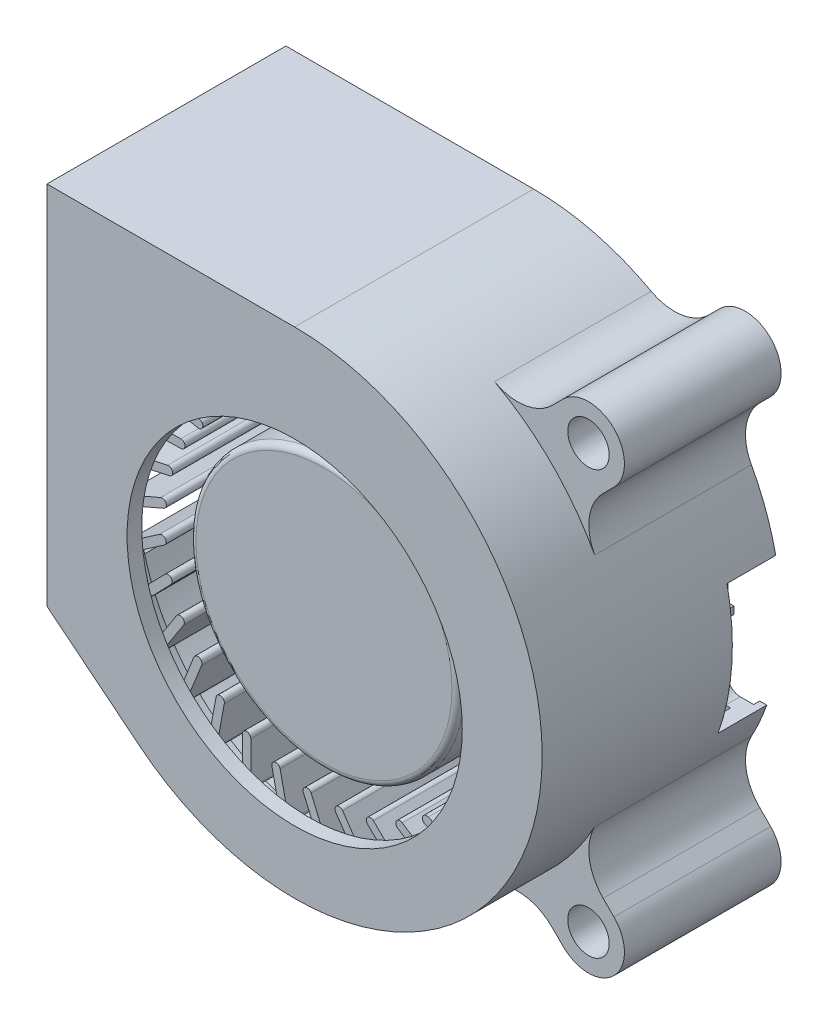
SolidWorks part; units mm, degrees
ref_plane "Спереди" through (0, 0, 0) normal (0, 0, 1) x (1, 0, 0)
ref_plane "Сверху" through (0, 0, 0) normal (0, 1, 0) x (1, 0, 0)
ref_plane "Справа" through (0, 0, 0) normal (1, 0, 0) x (0, 0, -1)
sketch "Эскиз1" plane through (0, 0, 0) normal (0, 0, 1) x (1, 0, 0)
  line L0 (-20.3193, 21.7023) -> (-20.3193, -8.2977)
  line L1 (-20.3193, -8.2977) -> (-12.7335, -14.4075)
  line L2 (-20.3193, 21.7023) -> (0, 21.7023)
  line L3 (0, 1.4023) -> (20.3, 21.7023) construction
  line L4 (20.3, 21.7023) -> (20.3, -18.8977) construction
  line L5 (20.3, -18.8977) -> (0, 1.4023) construction
  line L6 (20.3, -18.8977) -> (-20.3, -18.8977) construction
  line L7 (-20.3, -18.8977) -> (0, 1.4023) construction
  line L8 (-19.436, -13.8618) -> (-16.7482, -11.174)
  line L9 (-15.264, -18.0337) -> (-12.1159, -14.8856)
  line L10 (17.35, -18.8977) -> (0, -18.8977)
  line L11 (12.1159, -14.8856) -> (15.264, -18.0337)
  line L12 (19.436, -13.8618) -> (16.2879, -10.7137)
  line L13 (15.264, 20.8382) -> (12.1159, 17.6901)
  line L14 (19.436, 16.6663) -> (16.2879, 13.5182)
  line L15 (-20.3193, 20.5023) -> (0.1052, 20.502)
  line L16 (-17.6473, -5.904) -> (-20.3193, -7.0102)
  circle A0 centre (0, 0) radius 13.7477
  arc A1 (-12.7335, -14.4075) -> (0, 21.7023) centre (0, 1.4023) ccw
  circle A2 centre (17.35, 18.7523) radius 1.7
  circle A3 centre (-17.35, -15.9477) radius 1.7
  circle A4 centre (17.35, -15.9477) radius 1.7
  arc A5 (-19.436, -13.8618) -> (-15.264, -18.0337) centre (-17.35, -15.9477) ccw
  arc A6 (15.264, -18.0337) -> (19.436, -13.8618) centre (17.35, -15.9477) ccw
  arc A7 (19.436, 16.6663) -> (15.264, 20.8382) centre (17.35, 18.7523) ccw
  arc A8 (-17.6473, -5.904) -> (0.1052, 20.502) centre (0, 1.4023) ccw
  dimension "D1" = 30
  dimension "D2" = 20.3
  dimension "D3" = 27.4955
  dimension "D4" = 3.4
  dimension "D5" = 5.9
  dimension "D8" = 19.1
  dimension "D6" = 20.3193
  dimension "D7" = 1.4023
extrude "Бобышка-Вытянуть1" add sketch "Эскиз1" along normal blind 12.85 contours L14 A7 L13 A1 A2 | L11 A6 L12 A1 A4 | L8 A5 L9 A1 L1 A3 region at (13.7718, 19.1823, 0) region at (-14.8114, -12.8784, 0) region at (17.7801, -12.3696, 0)
extrude "Бобышка-Вытянуть2" add sketch "Эскиз1<4>" along normal blind 1.7 separate body contours L16 A8 L15 L0 A0 | A0 region at (-10.107, 19.9532, 0) region at (0, 0, 0)
sketch "Эскиз1<4>" plane through (0, 0, 0) normal (0, 0, 1) x (1, 0, 0) same geometry as "Эскиз1"
extrude "Бобышка-Вытянуть3" add sketch "Эскиз1<5>" along normal blind 19.6 contours A8 L16 L0 L1 A1 L2 L15 region at (-10.1596, 21.128, 0)
sketch "Эскиз1<5>" plane through (0, 0, 0) normal (0, 0, 1) x (1, 0, 0) same geometry as "Эскиз1"
extrude "Бобышка-Вытянуть4" add sketch "Эскиз1<6>" against normal blind 1.2 from vertex contours L16 A8 L15 L0 A0 region at (-10.107, 19.9532, 0) starting at point (-20.3193, 20.5023, 19.6)
sketch "Эскиз1<6>" plane through (0, 0, 0) normal (0, 0, 1) x (1, 0, 0) same geometry as "Эскиз1"
sketch "Эскиз2" plane through (0, 0, 0) normal (0, 0, -1) x (-1, 0, 0)
  line L8 (-10.3957, -0.3) -> (-19.6807, -0.3)
  line L9 (-0.3, 10.3957) -> (-0.2869, 21.1544)
  line L10 (10.3957, 0.3) -> (19.8766, 0.3)
  line L11 (0.3, -10.3957) -> (0.301, -18.3496)
  line L12 (19.887, -8.0245) -> (12.3908, -13.9826)
  line L13 (19.8505, 21.1544) -> (19.8766, 0.3)
  line L14 (19.8505, 21.1544) -> (0.3001, 21.1544)
  line L15 (-10.3957, 0.3) -> (-19.7234, 0.3)
  line L16 (0.3, 10.3957) -> (0.3001, 21.1544)
  line L17 (10.3957, -0.3) -> (19.8773, -0.3)
  line L18 (-0.3, -10.3957) -> (-0.301, -18.3496)
  line L19 (19.8773, -0.3) -> (19.887, -8.0245)
  arc A0 (0.301, -18.3496) -> (12.3908, -13.9826) centre (0, 1.4023) ccw
  arc A1 (10.3957, 0.3) -> (0.3, 10.3957) centre (0, 0) ccw
  arc A2 (0, 21.7023) -> (-12.1159, 17.6901) centre (0, 1.4023) ccw construction
  arc A5 (-0.2869, 21.1544) -> (-19.7234, 0.3) centre (0, 1.4023) ccw
  circle A6 centre (0, 0) radius 9.8
  arc A8 (-0.3, 10.3957) -> (-10.3957, 0.3) centre (0, 0) ccw
  arc A12 (-19.6807, -0.3) -> (-0.301, -18.3496) centre (0, 1.4023) ccw
  arc A13 (-10.3957, -0.3) -> (-0.3, -10.3957) centre (0, 0) ccw
  arc A14 (0.3, -10.3957) -> (10.3957, -0.3) centre (0, 0) ccw
extrude "Вырез-Вытянуть1" cut sketch "Эскиз2" against normal blind 0.5
sketch "Эскиз3" plane through (0, 0, 0) normal (0, 0, -1) x (-1, 0, 0)
  line L1 (-25.6875, -5.3927) -> (-16.4308, -5.3927)
  line L2 (-25.6875, -5.3927) -> (-25.6875, 5.6073)
  line L3 (-25.6875, 5.6073) -> (-16.4308, 5.6073)
  line L4 (-16.4308, -5.3927) -> (-16.4308, 5.6073)
  line L5 (-25.6875, -5.3927) -> (-16.4308, 5.6073) construction
  line L6 (-25.6875, 5.6073) -> (-16.4308, -5.3927) construction
extrude "Вырез-Вытянуть2" cut sketch "Эскиз3" against normal blind 4
sketch "Эскиз4" plane through (0, 0, 0) normal (0, 0, -1) x (-1, 0, 0)
  line L0 (1.85, -12.5557) -> (3.7573, -12.5557)
  line L2 (-3.7736, -9.046) -> (-3.7736, -12.5557)
  line L3 (-3.7736, -12.5557) -> (-1.85, -12.5557)
  line L4 (3.7573, -9.0528) -> (3.7573, -12.5557)
  line L5 (-0.0082, -9.8) -> (3.7573, -12.5557) construction
  line L6 (-3.7736, -12.5557) -> (-0.0082, -9.8) construction
  line L7 (-1.85, -18.9877) -> (1.85, -18.9877)
  line L8 (-1.85, -18.9877) -> (-1.85, -12.5557)
  line L10 (1.85, -18.9877) -> (1.85, -12.5557)
  line L11 (-1.85, -18.9877) -> (0, -14.4877) construction
  line L12 (0, -14.4877) -> (1.85, -18.9877) construction
  circle A0 centre (0, 0) radius 9.8 construction
  arc A1 (-3.7736, -9.046) -> (3.7573, -9.0528) centre (0, 0) ccw
  point P0 (-0.0082, -9.8)
  point P7 (0, -14.4877)
extrude "Вырез-Вытянуть3" cut sketch "Эскиз4" against normal blind 2
sketch "Эскиз5" plane through (0, -12.5557, 0) normal (0, 1, 0) x (1, 0, 0)
  line L0 (1.85, -1.7) -> (1.85, -2)
  line L1 (1.85, -2) -> (-1.85, -2)
  line L2 (-1.85, -2) -> (-1.85, -1.7)
  line L3 (2.8118, -1.7) -> (2.8118, -3.2)
  line L4 (1.85, -1.7) -> (3.7736, -1.7) construction
  line L5 (2.8118, -3.2) -> (-2.8036, -3.2)
  line L6 (-2.8036, -3.2) -> (-2.8036, -1.7)
  line L7 (-3.7573, -1.7) -> (-1.85, -1.7) construction
  line L8 (2.8118, -1.7) -> (1.85, -1.7)
  line L9 (-1.85, -1.7) -> (-2.8036, -1.7)
  dimension "D1" = 1.2
extrude "Бобышка-Вытянуть5" add sketch "Эскиз5" against normal up to next
fillet "Скругление1" radius 4 6 edges at (16.2879, 13.5182, 6.425) (12.1159, 17.6901, 6.425) (-12.1159, -14.8856, 6.425) (-16.7482, -11.174, 6.425) (16.2879, -10.7137, 6.425) (12.1159, -14.8856, 6.425)
fillet "Скругление2" radius 1 14 edges at (10.3957, -0.3, 0.25) (10.3957, 0.3, 0.25) (-19.887, -8.0245, 0.25) (-19.8773, -0.3, 0.25) (-10.3957, -0.3, 0.25) (-10.3957, 0.3, 0.25) (-19.8766, 0.3, 0.25) (-19.8505, 21.1544, 0.25) (-0.3001, 21.1544, 0.25) (0.2869, 21.1544, 0.25) (0.3, 10.3957, 0.25) (-0.3, 10.3957, 0.25) (16.4308, -5.3927, 1.1) (16.4308, 5.6073, 1.1)
ref_plane "Плоскость1" through (0, 0, 4.2) normal (0, 0, 1) x (1, 0, 0)
sketch "Эскиз6" plane through (0, 0, 4.2) normal (0, 0, 1) x (1, 0, 0)
  line L0 (-16.4475, 0) -> (-13.272, 1.3682) construction
  line L1 (-16.5836, 0.3159) -> (-13.4081, 1.6841)
  line L2 (-16.3114, -0.3159) -> (-13.1359, 1.0522)
  circle A0 centre (0, 0) radius 16.7732
  circle A1 centre (0, 0) radius 16.4475
  circle A2 centre (0, 0) radius 11
  arc A3 (-16.5836, 0.3159) -> (-16.3114, -0.3159) centre (-16.4475, 0) ccw
  arc A4 (-13.1359, 1.0522) -> (-13.4081, 1.6841) centre (-13.272, 1.3682) ccw
  point P7 (-14.8598, 0.6841)
extrude "Бобышка-Вытянуть6" add sketch "Эскиз6" along normal blind 1.2 separate body contours A4 L2 A3 A1 L1 A2 | L2 A4 L1 A1 A3 region at (0.1829, 15.9813, 4.2) region at (-14.7325, 0.7341, 4.2)
extrude "Бобышка-Вытянуть7" add sketch "Эскиз6<3>" along normal blind 13 contours L2 A4 L1 A1 A3 region at (-14.7325, 0.7341, 4.2)
sketch "Эскиз6<3>" plane through (0, 0, 4.2) normal (0, 0, 1) x (1, 0, 0) same geometry as "Эскиз6"
pattern_circular "Круговой массив6" count 32 over 360 about axis through (0, 0, 5.4) along (0, 0, -1) of "Бобышка-Вытянуть7"
extrude "Бобышка-Вытянуть8" add sketch "Эскиз6<4>" against normal blind 1.2 from offset 13 contours A3 L1 A1 A0 | L1 A3 A0 A1 region at (-16.7346, 0.2661, 4.2) region at (-16.5891, 0.0029, 4.2)
sketch "Эскиз6<4>" plane through (0, 0, 4.2) normal (0, 0, 1) x (1, 0, 0) same geometry as "Эскиз6"
extrude "Бобышка-Вытянуть9" add sketch "Эскиз6<5>" along normal blind 13 contours A2 region at (0, 0, 4.2)
sketch "Эскиз6<5>" plane through (0, 0, 4.2) normal (0, 0, 1) x (1, 0, 0) same geometry as "Эскиз6"
fillet "Скругление3" radius 0.5 1 edges at (11, 0, 17.2)
ref_axis "Eje1" through (-20.3193, -8.2977, 9.8) along (0, 1, 0)
ref_axis "Eje2" through (-20.3193, 6.7023, 0) along (0, 0, 1)
ref_plane "Plano medio salida" through (0, 6.7023, 0) normal (0, -1, 0) x (0, 0, 1)
